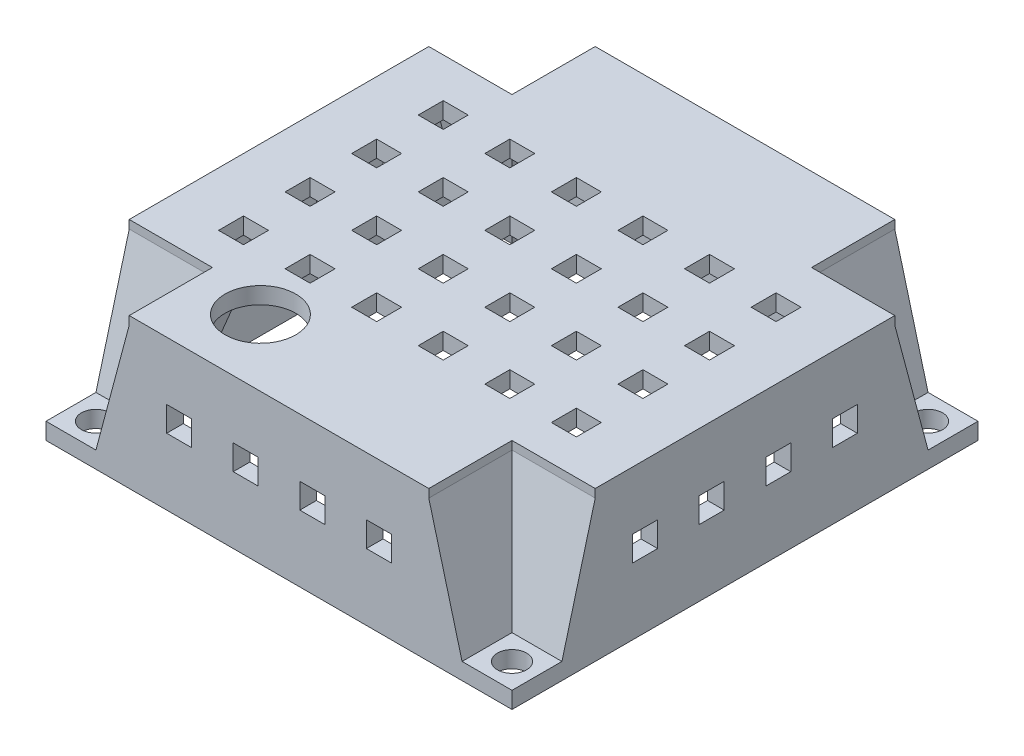
SolidWorks part; units mm, degrees
ref_plane "Спереди" through (0, 0, 0) normal (0, 0, 1) x (1, 0, 0)
ref_plane "Сверху" through (0, 0, 0) normal (0, 1, 0) x (1, 0, 0)
ref_plane "Справа" through (0, 0, 0) normal (1, 0, 0) x (0, 0, -1)
sketch "Эскиз1" plane through (0, 0, 0) normal (0, 1, 0) x (1, 0, 0)
  line L1 (28, -28) -> (-28, -28)
  line L2 (28, -28) -> (28, 28)
  line L3 (28, 28) -> (-28, 28)
  line L4 (-28, -28) -> (-28, 28)
  line L5 (28, -28) -> (-28, 28) construction
  line L6 (28, 28) -> (-28, -28) construction
  point P0 (0, 0)
  dimension "D1" = 56
  dimension "D2" = 56
extrude "Бобышка-Вытянуть1" add sketch "Эскиз1" along normal blind 18
sketch "Эскиз2" plane through (0, 18, 0) normal (0, 1, 0) x (1, 0, 0)
  line L0 (-28, 28) -> (-28, -28) construction
  line L5 (-29, 29) -> (-18, 29)
  line L6 (-29, 29) -> (-29, 18)
  line L7 (-29, 18) -> (-18, 18)
  line L8 (-18, 29) -> (-18, 18)
  line L9 (28, 28) -> (-28, 28) construction
  line L10 (28, -28) -> (28, 28) construction
  line L11 (29, 29) -> (18, 29)
  line L12 (29, 29) -> (29, 18)
  line L13 (29, 18) -> (18, 18)
  line L14 (18, 29) -> (18, 18)
  line L15 (-28, -28) -> (28, -28) construction
  line L16 (-29, -18) -> (-18, -18)
  line L17 (-29, -18) -> (-29, -29)
  line L18 (-29, -29) -> (-18, -29)
  line L19 (-18, -18) -> (-18, -29)
  line L20 (29, -18) -> (18, -18)
  line L21 (29, -18) -> (29, -29)
  line L22 (29, -29) -> (18, -29)
  line L23 (18, -18) -> (18, -29)
  dimension "D1" = 1
  dimension "D2" = 1
  dimension "D3" = 10
  dimension "D4" = 10
  dimension "D5" = 1
  dimension "D6" = 1
  dimension "D7" = 10
  dimension "D8" = 10
  dimension "D9" = 1
  dimension "D10" = 1
  dimension "D11" = 1
  dimension "D12" = 1
  dimension "D13" = 10
  dimension "D14" = 10
  dimension "D15" = 10
  dimension "D16" = 10
extrude "Вырез-Вытянуть2" cut sketch "Эскиз2" against normal blind 16
chamfer "Фаска1" distance 15 distance2 4 8 edges at (-23, 2, -18) (-18, 2, -23) (18, 2, 23) (23, 2, 18) (-18, 2, 23) (-23, 2, 18) (23, 2, -18) (18, 2, -23) first distance on face at (-23, 10, -18) first distance on face at (-18, 10, -23) first distance on face at (18, 10, 23) first distance on face at (23, 10, 18) first distance on face at (-18, 10, 23) first distance on face at (-23, 10, 18) first distance on face at (23, 10, -18) first distance on face at (18, 10, -23)
shell "Оболочка2" thickness 2 removed face at (0, 0, 0)
sketch "Эскиз5" plane through (0, 2, 0) normal (0, 1, 0) x (1, 0, 0)
  line L0 (-28, 28) -> (-28, 22) construction
  line L1 (-22, 28) -> (-28, 28) construction
  line L2 (22, 28) -> (28, 28) construction
  line L3 (28, 28) -> (28, 22) construction
  line L4 (-28, -22) -> (-28, -28) construction
  line L5 (-28, -28) -> (-22, -28) construction
  line L6 (28, -28) -> (22, -28) construction
  line L7 (28, -22) -> (28, -28) construction
  circle A0 centre (-25, 25) radius 1.75
  circle A1 centre (25, 25) radius 1.75
  circle A2 centre (-25, -25) radius 1.75
  circle A3 centre (25, -25) radius 1.75
  dimension "D3" = 3.5
  dimension "D6" = 3.5
  dimension "D9" = 3.5
  dimension "D12" = 3.5
  dimension "D1" = 3
  dimension "D2" = 3
  dimension "D4" = 3
  dimension "D5" = 3
  dimension "D7" = 3
  dimension "D8" = 3
  dimension "D10" = 3
  dimension "D11" = 3
extrude "Вырез-Вытянуть4" cut sketch "Эскиз5" against normal blind 15
sketch "Эскиз6" plane through (0, 18, 0) normal (0, 1, 0) x (1, 0, 0)
  line L0 (-28, 18) -> (-28, -18) construction
  line L1 (-21.5, 13.2333) -> (-18.5, 13.2333)
  line L2 (-21.5, 13.2333) -> (-21.5, 10.2333)
  line L3 (-21.5, 10.2333) -> (-18.5, 10.2333)
  line L4 (-18.5, 13.2333) -> (-18.5, 10.2333)
  line L5 (-21.5, 13.2333) -> (-18.5, 10.2333) construction
  line L6 (-21.5, 10.2333) -> (-18.5, 13.2333) construction
  line L8 (-28, 17.7333) -> (-17.7333, 17.7333) construction
  point P0 (-20, 11.7333)
  dimension "D1" = 8
  dimension "D2" = 6
  dimension "D3" = 3
  dimension "D4" = 3
extrude "Вырез-Вытянуть5" cut sketch "Эскиз6" against normal blind 2
pattern_linear "Линейный массив1" count 6 spacing 8 along (1, 0, 0) count 4 spacing 8 along (0, 0, 1) of "Вырез-Вытянуть5"
sketch "Эскиз7" plane through (0, 0, 28) normal (0, 0, 1) x (1, 0, 0)
  line L0 (-22, 2) -> (-28, 2) construction
  line L1 (-13.5, 11) -> (-10.5, 11)
  line L2 (-13.5, 11) -> (-13.5, 8)
  line L3 (-13.5, 8) -> (-10.5, 8)
  line L4 (-10.5, 11) -> (-10.5, 8)
  line L5 (-13.5, 11) -> (-10.5, 8) construction
  line L6 (-13.5, 8) -> (-10.5, 11) construction
  point P0 (-12, 9.5)
  dimension "D1" = 3
  dimension "D2" = 3
  dimension "D3" = 12
  dimension "D4" = 7.5
extrude "Вырез-Вытянуть6" cut sketch "Эскиз7" against normal through all
pattern_linear "Линейный массив2" count 4 spacing 8 along (1, 0, 0) of "Вырез-Вытянуть6"
sketch "Эскиз8" plane through (28, 0, 0) normal (1, 0, 0) x (0, 0, -1)
  line L0 (-22, 2) -> (-28, 2) construction
  line L1 (-13.5, 11) -> (-10.5, 11)
  line L2 (-13.5, 11) -> (-13.5, 8)
  line L3 (-13.5, 8) -> (-10.5, 8)
  line L4 (-10.5, 11) -> (-10.5, 8)
  line L5 (-13.5, 11) -> (-10.5, 8) construction
  line L6 (-13.5, 8) -> (-10.5, 11) construction
  point P0 (-12, 9.5)
  dimension "D1" = 3
  dimension "D2" = 3
  dimension "D3" = 12
  dimension "D4" = 7.5
extrude "Вырез-Вытянуть7" cut sketch "Эскиз8" against normal through all
pattern_linear "Линейный массив3" count 4 spacing 8 along (0, 0, -1) of "Вырез-Вытянуть7"
sketch "Эскиз9" plane through (0, 18, 0) normal (0, 1, 0) x (1, 0, 0)
  line L0 (-18, -28) -> (18, -28) construction
  line L1 (-17.7333, -28) -> (-17.7333, -17.7333) construction
  circle A0 centre (-10.2333, -20) radius 4.25
  dimension "D1" = 8.5
  dimension "D2" = 8
  dimension "D3" = 7.5
extrude "Вырез-Вытянуть8" cut sketch "Эскиз9" against normal blind 10
